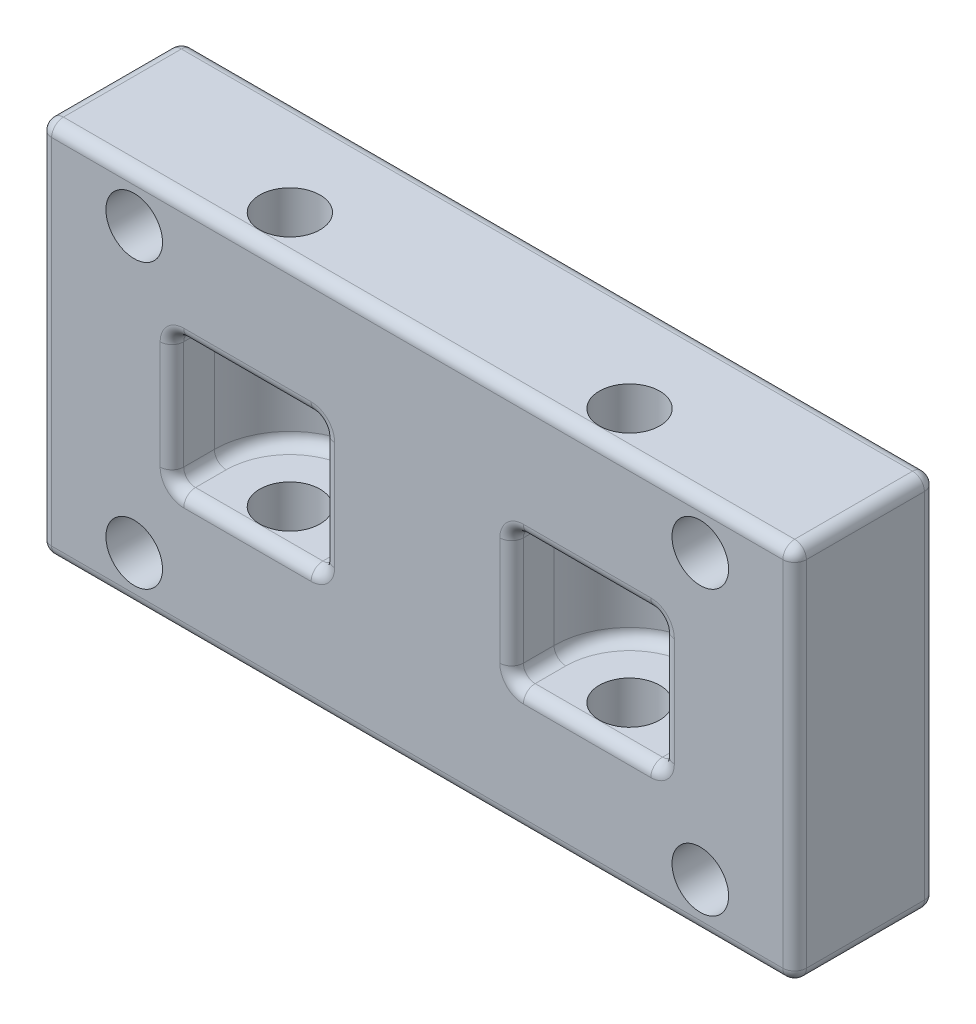
SolidWorks part; units mm, degrees
ref_plane "Front Plane" through (0, 0, 0) normal (0, 0, 1) x (1, 0, 0)
ref_plane "Top Plane" through (0, 0, 0) normal (0, 1, 0) x (1, 0, 0)
ref_plane "Right Plane" through (0, 0, 0) normal (1, 0, 0) x (0, 0, -1)
sketch "Sketch1" plane through (0, 0, 0) normal (0, 0, 1) x (1, 0, 0)
  line L1 (0, 0) -> (50.8, 0)
  line L2 (0, 0) -> (0, 25.4)
  line L3 (0, 25.4) -> (50.8, 25.4)
  line L4 (50.8, 0) -> (50.8, 25.4)
  dimension "D1" = 50.8
  dimension "D2" = 25.4
extrude "Boss-Extrude1" add sketch "Sketch1" along normal blind 9.525
ref_plane "Plane1" through (0, 12.7, 0) normal (0, 1, 0) x (1, 0, 0)
ref_plane "Plane2" through (25.4, 0, 0) normal (1, 0, 0) x (0, 0, -1)
sketch "Sketch2" plane through (0, 0, 9.525) normal (0, 0, 1) x (1, 0, 0)
  line L0 (0, 0) -> (50.8, 0) construction
  line L1 (0, 25.4) -> (0, 0) construction
  circle A0 centre (6.35, 22.225) radius 1.905
  dimension "D1" = 3.81
  dimension "D2" = 22.225
  dimension "D3" = 6.35
extrude "Cut-Extrude1" cut sketch "Sketch2" against normal through all
sketch "Sketch4" plane through (0, 12.7, 0) normal (0, 1, 0) x (1, 0, 0)
  line L7 (50.8, -9.525) -> (0, -9.525) construction
  line L8 (8.89, -6.6675) -> (8.89, -9.525)
  line L9 (19.05, -6.6675) -> (19.05, -9.525)
  line L10 (19.05, -9.525) -> (8.89, -9.525)
  line L11 (0, -9.525) -> (0, 0) construction
  arc A2 (19.05, -6.6675) -> (8.89, -6.6675) centre (13.97, -6.6675) ccw
  dimension "D1" = 10.16
  dimension "D2" = 2.8575
  dimension "D3" = 13.97
extrude "Cut-Extrude2" cut sketch "Sketch4" against normal mid plane 8.89
sketch "Sketch5" plane through (0, 25.4, 0) normal (0, 1, 0) x (1, 0, 0)
  line L0 (50.8, -9.525) -> (0, -9.525) construction
  line L1 (0, -9.525) -> (0, 0) construction
  circle A0 centre (13.97, -6.6675) radius 2.032
  dimension "D3" = 4.064
  dimension "D1" = 2.8575
  dimension "D2" = 13.97
extrude "Cut-Extrude3" cut sketch "Sketch5" against normal through all
mirror "Mirror1" about plane through (0, 12.7, 0) normal (0, 1, 0) of "Cut-Extrude1"
mirror "Mirror2" about plane through (25.4, 0, 0) normal (1, 0, 0) of "Cut-Extrude3", "Mirror1", "Cut-Extrude1", "Cut-Extrude2"
fillet "Fillet1" radius 0.7937 32 edges at (31.75, 8.255, 8.0962) (41.91, 8.255, 8.0962) (31.75, 17.145, 8.0962) (41.91, 17.145, 8.0962) (19.05, 8.255, 8.0962) (8.89, 8.255, 8.0962) (19.05, 17.145, 8.0962) (8.89, 17.145, 8.0962) (36.83, 8.255, 1.5875) (36.83, 17.145, 1.5875) (13.97, 8.255, 1.5875) (13.97, 17.145, 1.5875) (0, 25.4, 4.7625) (0, 12.7, 9.525) (0, 0, 4.7625) (0, 12.7, 0) (50.8, 0, 4.7625) (50.8, 12.7, 9.525) (50.8, 25.4, 4.7625) (50.8, 12.7, 0) (8.89, 12.7, 9.525) (13.97, 8.255, 9.525) (19.05, 12.7, 9.525) (13.97, 17.145, 9.525) (36.83, 17.145, 9.525) (36.83, 8.255, 9.525) (31.75, 12.7, 9.525) (41.91, 12.7, 9.525) (25.4, 25.4, 9.525) (25.4, 0, 9.525) (25.4, 0, 0) (25.4, 25.4, 0)
sketch "Sketch7" plane through (0, 0, 0) normal (0, 0, -1) x (-1, 0, 0)
  line L0 (-31.75, 6.35) -> (-31.75, 0) construction
  line L1 (-31.75, 6.35) -> (-50.8, 6.35) construction
  line L2 (-50.8, 0.7937) -> (-50.8, 24.6062) construction
  line L3 (-19.05, 6.35) -> (0, 6.35) construction
  line L4 (0, 24.6062) -> (0, 0.7937) construction
  line L5 (-0.7937, 0) -> (-50.0062, 0) construction
  line L6 (-31.75, 19.05) -> (-31.75, 25.4) construction
  line L7 (-50.0062, 25.4) -> (-0.7937, 25.4) construction
  circle A0 centre (-31.75, 19.05) radius 1.905
  circle A1 centre (-31.75, 6.35) radius 1.905
  circle A2 centre (-19.05, 19.05) radius 1.905
  circle A3 centre (-19.05, 6.35) radius 1.905
  point P8 (0, 0)
  dimension "D1" = 3.81
  dimension "D2" = 12.7
  dimension "D3" = 12.7
extrude "Cut-Extrude4" cut sketch "Sketch7" against normal blind 7.62
